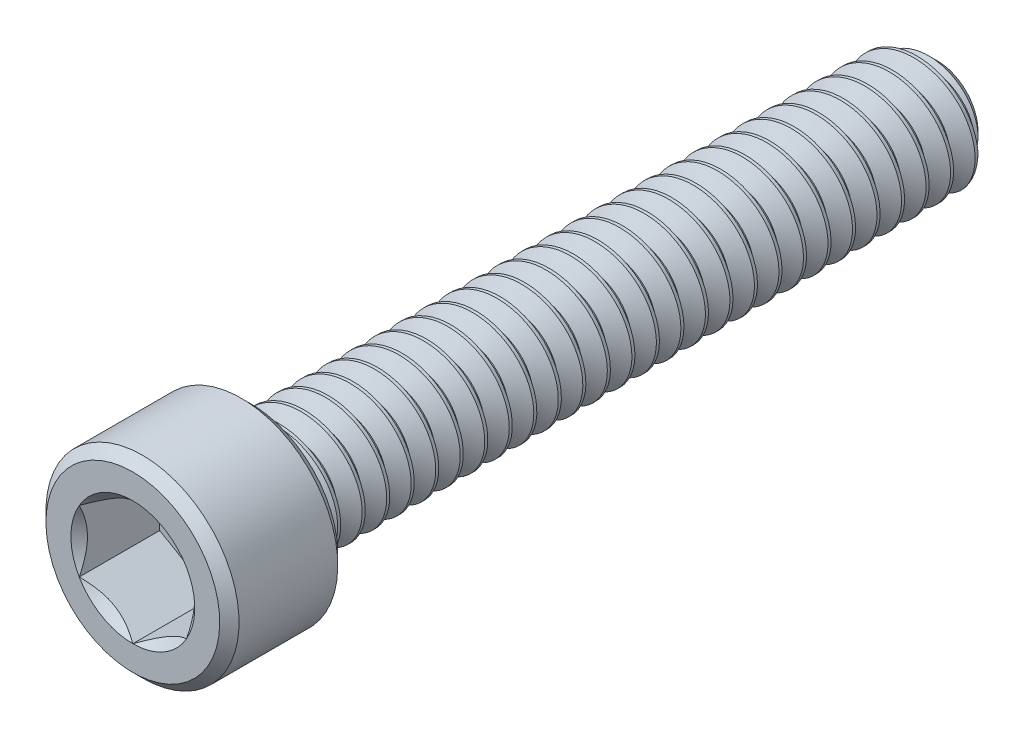
SolidWorks part; units mm, degrees
ref_plane "Front Plane" through (0, 0, 0) normal (0, 0, 1) x (1, 0, 0)
ref_plane "Top Plane" through (0, 0, 0) normal (0, 1, 0) x (1, 0, 0)
ref_plane "Right Plane" through (0, 0, 0) normal (1, 0, 0) x (0, 0, -1)
sketch "Sketch1" plane through (0, 0, 0) normal (1, 0, 0) x (0, 0, -1)
  line L0 (0, 0) -> (14.8844, 0) construction
  line L1 (0, 0) -> (0, 1.7859) construction
  line L2 (0, 1.7859) -> (2.1844, 1.7859) construction
  line L3 (2.1844, 1.7859) -> (2.1844, 1.0922) construction
  line L4 (2.1844, 1.0922) -> (14.8844, 1.0922) construction
  line L5 (14.8844, 1.0922) -> (14.8844, 0) construction
  line L6 (14.8844, 0) -> (14.8844, 0.4536) construction
  line L7 (2.1844, 1.7859) -> (14.8844, 1.7859) construction
  line L8 (14.8844, 0) -> (14.8844, -1.0922) construction
  line L9 (14.8844, -1.0922) -> (13.7505, -1.0922) construction
  point P6 (0, 0)
  dimension "Head Height" = 2.1844
  dimension "Head Diameter" = 3.5719
  dimension "Screw Length" = 12.7
  dimension "Screw Diameter" = 2.1844
  dimension "Thread Pitch" = 0.4536
  dimension "D1" = 1.1339
sketch "Sketch2" plane through (0, 0, 0) normal (0, 0, 1) x (1, 0, 0)
  line L1 (0, 1.1457) -> (-0.9922, 0.5728) construction
  line L2 (-0.9922, 0.5728) -> (-0.9922, -0.5728) construction
  line L3 (-0.9922, -0.5728) -> (0, -1.1457) construction
  line L4 (0, -1.1457) -> (0.9922, -0.5728) construction
  line L5 (0.9922, -0.5728) -> (0.9922, 0.5728) construction
  line L6 (0.9922, 0.5728) -> (0, 1.1457) construction
  circle A0 centre (0, 0) radius 1.7859 construction
  circle A1 centre (0, 0) radius 0.9922 construction
  dimension "D1" = 3.5719
  dimension "Drive Size" = 1.9844
sketch "Sketch3" plane through (0, 0, 0) normal (1, 0, 0) x (0, 0, -1)
  line L0 (0, 0) -> (14.8844, 0) construction
  line L1 (14.8844, 1.0922) -> (14.8844, 0) construction
  line L2 (2.1844, 1.0922) -> (14.8844, 1.0922) construction
  line L3 (2.1844, 1.7859) -> (2.1844, 1.0922) construction
  line L4 (0, 1.7859) -> (2.1844, 1.7859) construction
  line L5 (0, 0) -> (0, 1.7859) construction
  line L6 (0, 0) -> (14.8844, 0)
  line L7 (14.8844, 1.0922) -> (14.8844, 0)
  line L8 (2.1844, 1.0922) -> (14.8844, 1.0922)
  line L9 (2.1844, 1.7859) -> (2.1844, 1.0922)
  line L10 (0, 1.7859) -> (2.1844, 1.7859)
  line L11 (0, 0) -> (0, 1.7859)
revolve "Revolve1" add sketch "Sketch3" angle 360 about L6
chamfer "Chamfer1" distance 0.1786 angle 45 2 edges at (0, -1.7859, -2.1844) (0, -1.7859, 0)
chamfer "Chamfer2" distance 0.3402 angle 45 1 edges at (0, -1.0922, -14.8844)
sketch "Sketch4" plane through (0, 0, 0) normal (0, 0, 1) x (1, 0, 0)
  line L0 (-0.9922, -0.5728) -> (0, -1.1457) construction
  line L1 (0, -1.1457) -> (0.9922, -0.5728) construction
  line L2 (0.9922, -0.5728) -> (0.9922, 0.5728) construction
  line L3 (0.9922, 0.5728) -> (0, 1.1457) construction
  line L4 (0, 1.1457) -> (-0.9922, 0.5728) construction
  line L5 (-0.9922, 0.5728) -> (-0.9922, -0.5728) construction
  line L6 (-0.9922, -0.5728) -> (0, -1.1457)
  line L7 (0, -1.1457) -> (0.9922, -0.5728)
  line L8 (0.9922, -0.5728) -> (0.9922, 0.5728)
  line L9 (0.9922, 0.5728) -> (0, 1.1457)
  line L10 (0, 1.1457) -> (-0.9922, 0.5728)
  line L11 (-0.9922, 0.5728) -> (-0.9922, -0.5728)
extrude "Cut-Extrude1" cut sketch "Sketch4" against normal blind 1.4883
sketch "Sketch5" plane through (0, 0, 0) normal (0, 0, 1) x (1, 0, 0)
  circle A0 centre (0, 0) radius 1.1457
extrude "Cut-Extrude2" cut sketch "Sketch5" against normal through all draft 45
split "Split1" bodies to split 103 resulting bodies 105 106 split by face at (0, -1.6073, -2.1844)
ref_plane "Contact Plane 1" through (0, 0, 0) normal (0, 0, 1) x (1, 0, 0)
ref_plane "Contact Plane 2" through (0, 0, -2.1844) normal (0, 0, -1) x (-1, 0, 0)
ref_plane "Contact Plane 3" through (0, 0, -14.8844) normal (0, 0, -1) x (-1, 0, 0)
ref_axis "Center Axis 1" through (0, 0, -2.0058) along (0, 0, 1)
sketch "Sketch6" plane through (0, 0, -14.8844) normal (0, 0, -1) x (-1, 0, 0)
  circle A1 centre (0, 0) radius 1.0922
  dimension "D1" = 2.1844
curve "Helix/Spiral1" pitch 0.4536 height 13.1536 radius 1.0922 centre (0, 0, -14.8844) axis (0, 0, 1) start towards (0, 1, 0)
sketch "Sketch7" plane through (0, 0, 0) normal (1, 0, 0) x (0, 0, -1)
  line L0 (14.8844, 1.0922) -> (15.2813, 1.0922)
  line L1 (15.2813, 1.0922) -> (15.1112, 0.7976)
  line L2 (15.0545, 0.7976) -> (14.8844, 1.0922)
  line L3 (15.0545, 0.7976) -> (15.1112, 0.7976)
  line L4 (15.0828, 0.7976) -> (15.0828, 1.0922) construction
  line L5 (14.9694, 0.9449) -> (15.1962, 0.9449) construction
  point P9 (15.0828, 0.9449)
  dimension "D1" = 60
  dimension "D2" = 0.0567
  dimension "D3" = 0.2268
sweep "Cut-Sweep1" cut profiles "Sketch7" path "Helix/Spiral1" align with end faces yes
combine bodies "Combine1" operation type add bodies to combine 104 106
equation "\"D1@Sketch2\"=\"Head Diameter@Sketch1\""
equation "\"D1@Chamfer1\"=\"Head Diameter@Sketch1\"*.05"
equation "\"D1@Chamfer2\"=\"Thread Pitch@Sketch1\"*.75"
equation "\"D1@Cut-Extrude1\"=\"Drive Size@Sketch2\"*.75"
equation "\"D3@Helix/Spiral1\"=\"Screw Length@Sketch1\"+\"Thread Pitch@Sketch1\""
equation "\"D4@Helix/Spiral1\"=\"Thread Pitch@Sketch1\""
equation "\"D2@Sketch7\"=\"Thread Pitch@Sketch1\"/8"
equation "\"D3@Sketch7\"=\"Thread Pitch@Sketch1\"/2"
equation "\"D1@Sketch6\"=\"Screw Diameter@Sketch1\""
equation "\"D1@Sketch1\"=2.5*\"Thread Pitch@Sketch1\""
